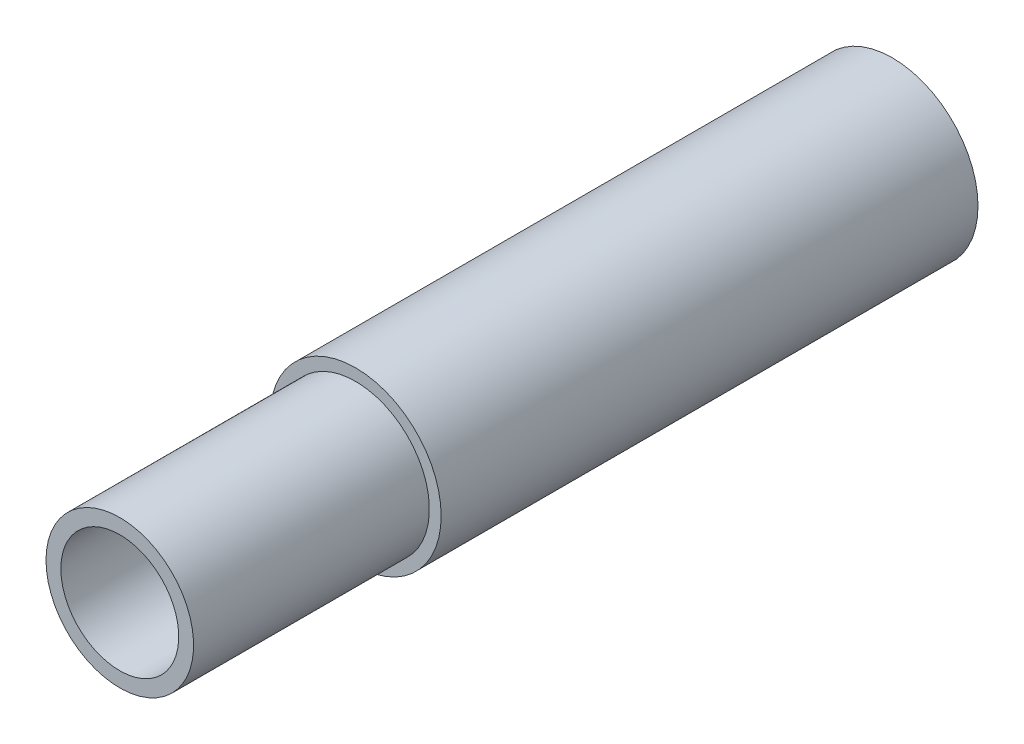
SolidWorks part; units mm, degrees
material "Silicon Rubber"
ref_plane "X-Y Datum" through (0, 0, 0) normal (0, 0, 1) x (1, 0, 0)
ref_plane "X-Z Datum" through (0, 0, 0) normal (0, 1, 0) x (1, 0, 0)
ref_plane "Y-Z Datum" through (0, 0, 0) normal (1, 0, 0) x (0, 0, -1)
sketch "Master Sketch" plane through (0, 0, 0) normal (0, 1, 0) x (1, 0, 0)
  line L0 (0, 0) -> (0, 50.8)
  line L2 (-9.525, 84.9884) -> (9.525, 84.9884) construction
  line L3 (-9.525, 95.5675) -> (9.525, 95.5675) construction
  line L4 (-9.525, 84.9884) -> (9.525, 84.9884) construction
  line L5 (-9.525, 95.5675) -> (9.525, 95.5675) construction
  line L6 (0, 84.9884) -> (0, 95.5675) construction
  line L7 (0, 50.8) -> (0, 104.0384)
  dimension "D1" = 19.05
  dimension "D4" = 50.8
sketch "Sketch9" plane through (0, 0, 0) normal (0, 1, 0) x (1, 0, 0)
  line L1 (0, 0) -> (0, 31.75)
  dimension "D1" = 31.75
sweep "Sweep1" add path "Sketch9" circular profile diameter 19.875 parameters "D3"=19.875
sweep "Cut-Sweep1" cut path "Sketch9<2>" circular profile diameter 15.875 parameters "D3"=15.875
sketch "Sketch9<2>" plane through (0, 0, 0) normal (0, 1, 0) x (1, 0, 0) same geometry as "Sketch9"
sketch "Sketch31" plane through (0, 0, 0) normal (0, 1, 0) x (1, 0, 0)
  line L0 (-9.525, 84.9884) -> (9.525, 84.9884) construction
  line L1 (-9.6754, 91.7558) -> (9.6754, 91.7558) construction
  line L2 (-9.525, 84.9884) -> (9.525, 84.9884) construction
  line L3 (-9.6754, 91.7558) -> (9.6754, 91.7558) construction
  line L4 (0, 91.7558) -> (0, 84.9884) construction
  line L5 (7.9375, 31.75) -> (-7.9375, 31.75) construction
  line L6 (7.9375, 31.75) -> (-7.9375, 31.75) construction
  line L7 (0, 31.75) -> (0, 104.0384)
  point P10 (0, 94.6667)
  dimension "D1" = 19.05
sweep "Sweep2" add path "Sketch31" circular profile diameter 23.05 parameters "D3"=23.05
sweep "Cut-Sweep2" cut path "Sketch31<2>" circular profile diameter 19.05 parameters "D3"=19.05
sketch "Sketch31<2>" plane through (0, 0, 0) normal (0, 1, 0) x (1, 0, 0) same geometry as "Sketch31"
